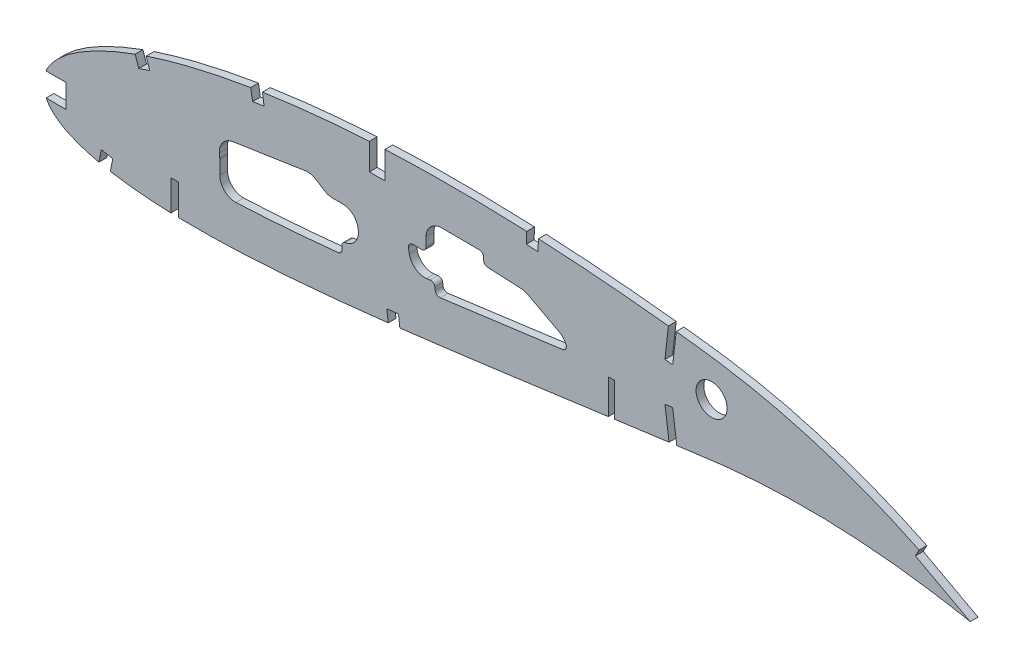
SolidWorks part; units mm, degrees
ref_plane "Front Plane" through (0, 0, 0) normal (0, 0, 1) x (1, 0, 0)
ref_plane "Top Plane" through (0, 0, 0) normal (0, 1, 0) x (1, 0, 0)
ref_plane "Right Plane" through (0, 0, 0) normal (1, 0, 0) x (0, 0, -1)
curve "Curve1"
  spline degree 3 poles (383.949, 0.5986, 0) (383.9196, 0.6168, 0) (383.802, 0.6894, 0) (383.5372, 0.8518, 0) (383.0962, 1.1224, 0) (382.4788, 1.4992, 0) (381.6856, 1.9812, 0) (380.716, 2.5651, 0) (379.5708, 3.249, 0) (378.2502, 4.0295, 0) (376.7543, 4.9032, 0) (375.0838, 5.8664, 0) (373.2387, 6.9137, 0) (371.2197, 8.0407, 0) (369.0276, 9.2423, 0) (366.6628, 10.5128, 0) (364.1261, 11.8459, 0) (361.4185, 13.2358, 0) (358.5405, 14.6749, 0) (355.4934, 16.1571, 0) (352.2782, 17.675, 0) (348.8962, 19.2207, 0) (345.3491, 20.7877, 0) (341.638, 22.3663, 0) (337.765, 23.9497, 0) (333.7318, 25.5289, 0) (329.5407, 27.0966, 0) (325.1933, 28.6428, 0) (320.6929, 30.1607, 0) (316.0417, 31.6403, 0) (311.2431, 33.0737, 0) (306.2997, 34.4516, 0) (301.2157, 35.767, 0) (295.9944, 37.0101, 0) (290.6401, 38.1728, 0) (285.1572, 39.2479, 0) (279.5502, 40.2249, 0) (273.8346, 41.1028, 0) (268.1025, 41.8331, 0) (262.3821, 42.5494, 0) (256.6703, 43.2222, 0) (250.8886, 43.8666, 0) (245.0428, 44.4788, 0) (239.1384, 45.057, 0) (233.1816, 45.5987, 0) (227.1785, 46.1022, 0) (221.135, 46.5647, 0) (215.0573, 46.9856, 0) (208.9515, 47.361, 0) (202.8242, 47.6908, 0) (196.6815, 47.9725, 0) (190.5298, 48.2044, 0) (184.3757, 48.385, 0) (178.2255, 48.5125, 0) (172.0859, 48.5861, 0) (165.9633, 48.6039, 0) (159.8643, 48.5655, 0) (153.7954, 48.4696, 0) (147.7632, 48.3149, 0) (141.7741, 48.1011, 0) (135.8345, 47.8283, 0) (129.951, 47.4942, 0) (124.1299, 47.1009, 0) (118.3778, 46.6469, 0) (112.701, 46.1319, 0) (107.1053, 45.5581, 0) (101.5971, 44.9239, 0) (96.1822, 44.2312, 0) (90.8666, 43.4813, 0) (85.6562, 42.6738, 0) (80.5566, 41.8111, 0) (75.5733, 40.894, 0) (70.7116, 39.9252, 0) (65.9768, 38.9049, 0) (61.3739, 37.8363, 0) (56.9076, 36.7211, 0) (52.5828, 35.5615, 0) (48.4038, 34.3602, 0) (44.375, 33.1199, 0) (40.5009, 31.842, 0) (36.7845, 30.5314, 0) (33.2304, 29.1889, 0) (29.8413, 27.8188, 0) (26.6212, 26.4228, 0) (23.5724, 25.0052, 0) (20.6984, 23.5677, 0) (18.0014, 22.1143, 0) (15.4839, 20.6472, 0) (13.1483, 19.1691, 0) (10.9958, 17.6837, 0) (9.0293, 16.1921, 0) (7.2493, 14.698, 0) (5.6571, 13.2036, 0) (4.255, 11.71, 0) (3.0428, 10.2198, 0) (2.0222, 8.7343, 0) (1.1933, 7.2547, 0) (0.558, 5.7822, 0) (0.1157, 4.3176, 0) (-0.1263, 2.863, 0) (-0.1866, 1.4174, 0) (-0.0621, 0.4718, 0) (0, 0, 0) knots 0 0 0 0 0.000254 0.001015 0.002283 0.004057 0.006331 0.009105 0.012374 0.016134 0.02038 0.025106 0.030306 0.035972 0.0421 0.048678 0.055702 0.06316 0.071046 0.07935 0.088063 0.097176 0.106678 0.116562 0.126814 0.137428 0.148394 0.1597 0.171338 0.183298 0.19557 0.208144 0.221012 0.234162 0.247587 0.261277 0.275223 0.289414 0.303771 0.317689 0.331784 0.34604 0.360444 0.374983 0.38964 0.404403 0.419257 0.434187 0.449177 0.464215 0.479284 0.49437 0.509458 0.524532 0.539579 0.554583 0.56953 0.584403 0.599191 0.613877 0.628447 0.642889 0.657186 0.671326 0.685294 0.699078 0.712665 0.726043 0.739198 0.752118 0.764792 0.777208 0.789356 0.801224 0.812804 0.824083 0.835055 0.84571 0.856038 0.866034 0.875689 0.884998 0.893953 0.902553 0.910789 0.918661 0.926166 0.933303 0.940071 0.946475 0.952518 0.958205 0.963547 0.968557 0.97325 0.977651 0.981787 0.985694 0.989415 0.993001 0.996508 1 1 1 1
curve "Curve2"
  spline degree 3 poles (0, 0, 0) (0.0986, -0.4654, 0) (0.2962, -1.3985, 0) (0.8332, -2.7416, 0) (1.5434, -4.0328, 0) (2.4415, -5.2686, 0) (3.5218, -6.4485, 0) (4.7818, -7.574, 0) (6.2202, -8.6443, 0) (7.8352, -9.659, 0) (9.6244, -10.6191, 0) (11.5859, -11.5241, 0) (13.7178, -12.3737, 0) (16.0178, -13.1667, 0) (18.4831, -13.9043, 0) (21.1113, -14.5848, 0) (23.8995, -15.2091, 0) (26.845, -15.7756, 0) (29.9446, -16.2848, 0) (33.195, -16.7366, 0) (36.593, -17.1311, 0) (40.1351, -17.4676, 0) (43.8179, -17.7467, 0) (47.6377, -17.9687, 0) (51.5909, -18.1343, 0) (55.6735, -18.2428, 0) (59.8817, -18.2959, 0) (64.2115, -18.2945, 0) (68.6589, -18.238, 0) (73.2199, -18.1297, 0) (77.8902, -17.9689, 0) (82.6657, -17.7575, 0) (87.5419, -17.4976, 0) (92.5144, -17.1902, 0) (97.5791, -16.8365, 0) (102.7313, -16.4394, 0) (107.9665, -16, 0) (113.2801, -15.5207, 0) (118.6674, -15.0039, 0) (124.1237, -14.4514, 0) (129.6442, -13.8657, 0) (135.2241, -13.2487, 0) (140.8584, -12.6036, 0) (146.5422, -11.9317, 0) (152.2705, -11.2369, 0) (158.0381, -10.5203, 0) (163.84, -9.7848, 0) (169.6711, -9.0339, 0) (175.5259, -8.2674, 0) (181.3995, -7.4908, 0) (187.2862, -6.7036, 0) (193.1809, -5.9096, 0) (199.0781, -5.1115, 0) (204.9721, -4.3094, 0) (210.8578, -3.5066, 0) (216.7295, -2.7054, 0) (222.5817, -1.9059, 0) (228.409, -1.112, 0) (234.2055, -0.3236, 0) (239.9659, 0.4577, 0) (245.6847, 1.2295, 0) (251.3565, 1.9909, 0) (256.9754, 2.7413, 0) (262.5357, 3.4812, 0) (267.9487, 4.188, 0) (273.2002, 4.8993, 0) (278.3079, 5.4825, 0) (283.3519, 5.9802, 0) (288.3377, 6.3883, 0) (293.259, 6.7125, 0) (298.1104, 6.9553, 0) (302.886, 7.1201, 0) (307.5799, 7.2116, 0) (312.186, 7.2323, 0) (316.6983, 7.1886, 0) (321.1107, 7.0842, 0) (325.4171, 6.9238, 0) (329.6115, 6.7126, 0) (333.688, 6.4566, 0) (337.6405, 6.1594, 0) (341.4634, 5.828, 0) (345.1508, 5.4673, 0) (348.6971, 5.0813, 0) (352.0971, 4.6782, 0) (355.3453, 4.2606, 0) (358.4369, 3.8354, 0) (361.3669, 3.4069, 0) (364.1307, 2.9806, 0) (366.7239, 2.5605, 0) (369.1422, 2.1521, 0) (371.3821, 1.7594, 0) (373.4394, 1.3862, 0) (375.3115, 1.0371, 0) (376.9946, 0.7139, 0) (378.4864, 0.4219, 0) (379.7842, 0.1625, 0) (380.886, -0.0608, 0) (381.79, -0.247, 0) (382.4947, -0.3932, 0) (382.9989, -0.4995, 0) (383.3019, -0.5627, 0) (383.4365, -0.5914, 0) (383.4701, -0.5986, 0) knots 0 0 0 0 0.003638 0.007293 0.011028 0.014901 0.018963 0.023258 0.027821 0.032679 0.037853 0.043362 0.049215 0.055422 0.061989 0.068918 0.076211 0.083868 0.091887 0.100266 0.109 0.118085 0.127515 0.137285 0.147388 0.157816 0.168563 0.179619 0.190977 0.202627 0.21456 0.226767 0.239236 0.251959 0.264924 0.27812 0.291536 0.30516 0.318981 0.332985 0.347163 0.361499 0.375981 0.390597 0.405333 0.420175 0.43511 0.450124 0.465203 0.480333 0.495501 0.51069 0.525887 0.541078 0.556247 0.571382 0.586466 0.601485 0.616424 0.631269 0.646007 0.660621 0.675098 0.689423 0.703582 0.716908 0.730009 0.742952 0.755726 0.76832 0.780724 0.792927 0.804916 0.816679 0.828204 0.839475 0.850481 0.861208 0.871639 0.881763 0.891564 0.901027 0.910139 0.918884 0.927249 0.935221 0.942785 0.949928 0.956638 0.962904 0.968712 0.974054 0.978918 0.983297 0.98718 0.990561 0.993433 0.995791 0.99763 0.998946 0.999737 1 1 1 1
sketch "Sketch1" plane through (0, 0, 0) normal (0, 0, 1) x (1, 0, 0)
  line L23 (383.4597, -0.5986) -> (387.1511, -1.386)
  line L24 (383.9386, 0.5986) -> (387.1511, -1.386)
  spline S4 degree 3 poles (0, 0) (0.0986, -0.4654) (0.2962, -1.3984) (0.8332, -2.7416) (1.5433, -4.0327) (2.4415, -5.2684) (3.5217, -6.4484) (4.7816, -7.5738) (6.22, -8.6441) (7.835, -9.6587) (9.6242, -10.6188) (11.5856, -11.5238) (13.7174, -12.3733) (16.0173, -13.1663) (18.4826, -13.9039) (21.1108, -14.5844) (23.8989, -15.2087) (26.8443, -15.7751) (29.9438, -16.2844) (33.1941, -16.7361) (36.592, -17.1306) (40.134, -17.4671) (43.8167, -17.7462) (47.6365, -17.9682) (51.5895, -18.1338) (55.672, -18.2423) (59.88, -18.2954) (64.2098, -18.294) (68.657, -18.2375) (73.2179, -18.1293) (77.8881, -17.9684) (82.6634, -17.757) (87.5395, -17.4972) (92.5119, -17.1897) (97.5764, -16.836) (102.7286, -16.439) (107.9636, -15.9995) (113.2771, -15.5202) (118.6642, -15.0035) (124.1204, -14.451) (129.6407, -13.8653) (135.2204, -13.2483) (140.8546, -12.6033) (146.5382, -11.9314) (152.2664, -11.2365) (158.0338, -10.52) (163.8356, -9.7845) (169.6665, -9.0336) (175.5212, -8.2672) (181.3946, -7.4906) (187.2811, -6.7034) (193.1757, -5.9095) (199.0727, -5.1113) (204.9666, -4.3092) (210.8521, -3.5065) (216.7237, -2.7054) (222.5757, -1.9059) (228.4028, -1.112) (234.1992, -0.3236) (239.9594, 0.4576) (245.6781, 1.2294) (251.3497, 1.9908) (256.9684, 2.7413) (262.5286, 3.4811) (267.9415, 4.1879) (273.1928, 4.8992) (278.3003, 5.4823) (283.3443, 5.98) (288.3299, 6.3881) (293.2511, 6.7123) (298.1023, 6.9552) (302.8778, 7.1199) (307.5715, 7.2114) (312.1776, 7.2321) (316.6897, 7.1884) (321.102, 7.084) (325.4083, 6.9236) (329.6026, 6.7124) (333.679, 6.4564) (337.6313, 6.1592) (341.4541, 5.8278) (345.1414, 5.4671) (348.6876, 5.0812) (352.0875, 4.6781) (355.3357, 4.2605) (358.4272, 3.8353) (361.3571, 3.4068) (364.1208, 2.9805) (366.7139, 2.5604) (369.1322, 2.1521) (371.372, 1.7594) (373.4293, 1.3862) (375.3013, 1.0371) (376.9844, 0.7139) (378.4761, 0.4219) (379.7739, 0.1625) (380.8757, -0.0608) (381.7796, -0.247) (382.4844, -0.3932) (382.9885, -0.4994) (383.2915, -0.5627) (383.4261, -0.5914) (383.4597, -0.5986) knots 0 0 0 0 0.003638 0.007293 0.011028 0.014901 0.018963 0.023258 0.027821 0.032679 0.037853 0.043362 0.049215 0.055422 0.061989 0.068918 0.076211 0.083868 0.091887 0.100266 0.109 0.118085 0.127515 0.137285 0.147388 0.157816 0.168563 0.179619 0.190977 0.202627 0.21456 0.226767 0.239236 0.251959 0.264924 0.27812 0.291536 0.30516 0.318981 0.332985 0.347163 0.361499 0.375981 0.390597 0.405333 0.420175 0.43511 0.450124 0.465203 0.480333 0.495501 0.51069 0.525887 0.541078 0.556247 0.571382 0.586466 0.601485 0.616424 0.631269 0.646007 0.660621 0.675098 0.689423 0.703582 0.716908 0.730009 0.742952 0.755726 0.76832 0.780724 0.792927 0.804916 0.816679 0.828204 0.839475 0.850481 0.861208 0.871639 0.881763 0.891564 0.901027 0.910139 0.918884 0.927249 0.935221 0.942785 0.949928 0.956638 0.962904 0.968712 0.974054 0.978918 0.983297 0.98718 0.990561 0.993433 0.995791 0.99763 0.998946 0.999737 1 1 1 1
  spline S5 degree 3 poles (383.9386, 0.5986) (383.9092, 0.6167) (383.7916, 0.6893) (383.5268, 0.8518) (383.0858, 1.1223) (382.4685, 1.4991) (381.6752, 1.9811) (380.7057, 2.565) (379.5606, 3.2489) (378.24, 4.0294) (376.7441, 4.9031) (375.0736, 5.8662) (373.2286, 6.9135) (371.2097, 8.0405) (369.0176, 9.242) (366.6529, 10.5125) (364.1162, 11.8456) (361.4087, 13.2354) (358.5307, 14.6745) (355.4837, 16.1566) (352.2687, 17.6745) (348.8867, 19.2201) (345.3398, 20.7871) (341.6288, 22.3657) (337.7559, 23.949) (333.7228, 25.5282) (329.5317, 27.0959) (325.1845, 28.642) (320.6843, 30.1598) (316.0332, 31.6395) (311.2346, 33.0728) (306.2914, 34.4507) (301.2076, 35.766) (295.9864, 37.0091) (290.6322, 38.1717) (285.1495, 39.2469) (279.5426, 40.2238) (273.8272, 41.1017) (268.0952, 41.832) (262.375, 42.5482) (256.6633, 43.2211) (250.8818, 43.8654) (245.0361, 44.4776) (239.1319, 45.0558) (233.1753, 45.5974) (227.1724, 46.1009) (221.129, 46.5635) (215.0515, 46.9843) (208.9459, 47.3597) (202.8187, 47.6895) (196.6762, 47.9712) (190.5246, 48.2031) (184.3707, 48.3836) (178.2206, 48.5111) (172.0812, 48.5848) (165.9588, 48.6026) (159.86, 48.5642) (153.7912, 48.4683) (147.7592, 48.3136) (141.7702, 48.0998) (135.8308, 47.827) (129.9475, 47.4929) (124.1266, 47.0997) (118.3746, 46.6456) (112.6979, 46.1306) (107.1024, 45.5568) (101.5944, 44.9227) (96.1796, 44.23) (90.8641, 43.4801) (85.6539, 42.6727) (80.5544, 41.81) (75.5713, 40.8929) (70.7097, 39.9241) (65.975, 38.9039) (61.3722, 37.8353) (56.906, 36.7201) (52.5814, 35.5606) (48.4025, 34.3593) (44.3738, 33.119) (40.4998, 31.8412) (36.7835, 30.5306) (33.2295, 29.1881) (29.8405, 27.818) (26.6204, 26.4221) (23.5718, 25.0045) (20.6979, 23.5671) (18.0009, 22.1137) (15.4834, 20.6466) (13.148, 19.1685) (10.9955, 17.6833) (9.029, 16.1917) (7.2491, 14.6976) (5.657, 13.2033) (4.2548, 11.7097) (3.0427, 10.2196) (2.0221, 8.734) (1.1932, 7.2545) (0.558, 5.782) (0.1157, 4.3174) (-0.1263, 2.8629) (-0.1866, 1.4173) (-0.0621, 0.4717) (0, 0) knots 0 0 0 0 0.000254 0.001015 0.002283 0.004057 0.006331 0.009105 0.012374 0.016134 0.02038 0.025106 0.030306 0.035972 0.0421 0.048678 0.055702 0.06316 0.071046 0.07935 0.088063 0.097176 0.106678 0.116562 0.126814 0.137428 0.148394 0.1597 0.171338 0.183298 0.19557 0.208144 0.221012 0.234162 0.247587 0.261277 0.275223 0.289414 0.303771 0.317689 0.331784 0.34604 0.360444 0.374983 0.38964 0.404403 0.419257 0.434187 0.449177 0.464215 0.479284 0.49437 0.509458 0.524532 0.539579 0.554583 0.56953 0.584403 0.599191 0.613877 0.628447 0.642889 0.657186 0.671326 0.685294 0.699078 0.712665 0.726043 0.739198 0.752118 0.764792 0.777208 0.789356 0.801224 0.812804 0.824083 0.835055 0.84571 0.856038 0.866034 0.875689 0.884998 0.893953 0.902553 0.910789 0.918661 0.926166 0.933303 0.940071 0.946475 0.952518 0.958205 0.963547 0.968557 0.97325 0.977651 0.981787 0.985694 0.989415 0.993001 0.996508 1 1 1 1
extrude "Boss-Extrude1" add sketch "Sketch1" along normal blind 3.175
sketch "Sketch2" plane through (0, 0, 0) normal (0, 0, -1) x (-1, 0, 0)
  line L0 (-232.8305, 13.2238) -> (-230.2905, 13.2238)
  line L1 (-232.8305, -0.5032) -> (-232.8305, -2.8497)
  line L2 (-232.8305, 13.2238) -> (-232.8305, -0.5032)
  line L4 (-232.8305, -2.8497) -> (-230.2905, -1.6764)
  line L5 (-230.2905, -1.6764) -> (-230.2905, -0.5032)
  line L7 (-139.168, 47.9082) -> (-139.168, 36.8678)
  line L8 (-139.168, 36.8678) -> (-132.818, 36.8678)
  line L9 (-139.168, 47.9082) -> (-139.168, 49.4489)
  line L10 (-55.0305, -5.6829) -> (-55.0305, -17.799)
  line L12 (-139.168, 49.4489) -> (-132.818, 49.1679)
  line L13 (-132.818, 49.1679) -> (-132.818, 47.9082)
  line L14 (-51.8555, -5.6829) -> (-51.8555, -17.799)
  line L16 (-55.0305, -5.6829) -> (-51.8555, -5.6829)
  line L17 (-55.0305, -17.799) -> (-55.0305, -19.968)
  line L19 (-132.818, 47.9082) -> (-132.818, 36.8678)
  line L20 (-55.0305, -19.968) -> (-51.8555, -18.5014)
  line L21 (-51.8555, -18.5014) -> (-51.8555, -17.799)
  line L22 (-230.2905, 13.2238) -> (-230.2905, -0.5032)
extrude "Cut-Extrude1" cut sketch "Sketch2" against normal blind 7.62
sketch "Sketch3" plane through (0, 0, 0) normal (0, 0, -1) x (-1, 0, 0)
  circle A1 centre (-272.4199, 26.2554) radius 6.35
extrude "Cut-Extrude2" cut sketch "Sketch3" against normal blind 7.62
sketch "Sketch4" plane through (0, 0, 3.175) normal (0, 0, 1) x (1, 0, 0)
  line L0 (253.3978, 15.0563) -> (255.0785, 2.468)
  line L1 (253.3978, 15.0563) -> (255.0785, 2.468)
  line L2 (256.5449, 15.4765) -> (253.3978, 15.0563)
  line L3 (256.5449, 15.4765) -> (253.3978, 15.0563)
  line L4 (254.8081, 43.5209) -> (253.3898, 30.9004)
  line L5 (254.8081, 43.5209) -> (253.3898, 30.9004)
  line L6 (197.0245, 48.0319) -> (196.82, 43.2872)
  line L7 (197.0245, 48.0319) -> (196.82, 43.2872)
  line L8 (84.4023, 42.5499) -> (85.1717, 37.8779)
  line L9 (84.4023, 42.5499) -> (85.1717, 37.8779)
  line L10 (139.9591, -7.9331) -> (140.5078, -12.6647)
  line L11 (139.9591, -7.9331) -> (140.5078, -12.6647)
  line L12 (144.6885, -7.3719) -> (139.9591, -7.9331)
  line L13 (144.6885, -7.3719) -> (139.9591, -7.9331)
  line L14 (37.2314, 30.8049) -> (38.732, 26.3414)
  line L15 (37.2314, 30.8049) -> (38.732, 26.3414)
  line L16 (23.4683, -9.9368) -> (22.5446, -14.6116)
  line L17 (23.4683, -9.9368) -> (22.5446, -14.6116)
  line L18 (28.1358, -10.8598) -> (23.4683, -9.9368)
  line L19 (28.1358, -10.8598) -> (23.4683, -9.9368)
  line L20 (-0.4208, 6.5685) -> (9.1042, 6.5685)
  line L21 (-0.4208, 6.5685) -> (9.1042, 6.5685)
  line L22 (9.1042, -2.9565) -> (9.1042, 6.5685)
  line L23 (9.1042, -2.9565) -> (9.1042, 6.5685)
  line L24 (-0.4208, -2.9565) -> (9.1042, -2.9565)
  line L25 (-0.4208, -2.9565) -> (9.1042, -2.9565)
  line L26 (27.1866, -15.6474) -> (28.1358, -10.8598)
  line L27 (27.1866, -15.6474) -> (28.1358, -10.8598)
  line L28 (43.2462, 27.8589) -> (41.731, 32.3666)
  line L29 (43.2462, 27.8589) -> (41.731, 32.3666)
  line L30 (38.732, 26.3414) -> (43.2462, 27.8589)
  line L31 (38.732, 26.3414) -> (43.2462, 27.8589)
  line L32 (89.8796, 38.5972) -> (89.1598, 43.3084)
  line L33 (89.8796, 38.5972) -> (89.1598, 43.3084)
  line L34 (85.1717, 37.8779) -> (89.8796, 38.5972)
  line L35 (85.1717, 37.8779) -> (89.8796, 38.5972)
  line L36 (145.2504, -12.1074) -> (144.6885, -7.3719)
  line L37 (145.2504, -12.1074) -> (144.6885, -7.3719)
  line L38 (201.5767, 43.0552) -> (201.8123, 47.81)
  line L39 (201.5767, 43.0552) -> (201.8123, 47.81)
  line L40 (196.82, 43.2872) -> (201.5767, 43.0552)
  line L41 (196.82, 43.2872) -> (201.5767, 43.0552)
  line L42 (258.2214, 2.8872) -> (256.5449, 15.4765)
  line L43 (258.2214, 2.8872) -> (256.5449, 15.4765)
  line L44 (256.5449, 30.5458) -> (258.0069, 43.1557)
  line L45 (256.5449, 30.5458) -> (258.0069, 43.1557)
  line L46 (253.3898, 30.9004) -> (256.5449, 30.5458)
  line L47 (253.3898, 30.9004) -> (256.5449, 30.5458)
  line L48 (-0.4208, -2.9565) -> (-0.4208, 6.5685)
  line L49 (22.5446, -14.6116) -> (21.6044, -19.3694)
  line L50 (21.6044, -19.3694) -> (26.2707, -20.2914)
  line L51 (26.2707, -20.2914) -> (27.1866, -15.6474)
  line L52 (84.4023, 42.5499) -> (89.1598, 43.3084)
  line L53 (140.5078, -12.6647) -> (145.2504, -12.1074)
  line L54 (197.0245, 48.0319) -> (201.8123, 47.81)
  line L55 (254.8081, 43.5209) -> (258.0069, 43.1557)
  line L56 (255.0785, 2.468) -> (255.3213, 0.6492)
  line L57 (255.3213, 0.6492) -> (258.4684, 1.0693)
  line L58 (258.4684, 1.0693) -> (258.2214, 2.8872)
  spline S0 degree 3 poles (-319.8285, 964.7154) (438.4345, -55.4641) (67.7324, 173.0911) (-130.5432, -104.2984) (209.618, -954.1931) knots -109.467711 -109.467711 -109.467711 -109.467711 0.273428 65.100383 65.100383 65.100383 65.100383 only from (41.731, 32.3666) to (37.2314, 30.8049)
  spline S1 degree 3 poles (41.731, 32.3666) (41.3193, 32.2289) (39.8151, 31.7207) (38.3166, 31.1959) (37.2314, 30.8049) knots 0 0 0 0 0.273428 1 1 1 1
extrude "Cut-Extrude3" cut sketch "Sketch4" against normal through all
sketch "Sketch5" plane through (0, 0, 3.175) normal (0, 0, 1) x (1, 0, 0)
  line L0 (127.2472, 20.1038) -> (116.054, 20.1038)
  line L3 (108.9829, 24.5572) -> (71.3232, 18.8038)
  line L9 (71.7945, 11.0811) -> (71.7945, -1.3909)
  line L10 (121.9103, 2.1782) -> (121.3808, 6.7439)
  line L11 (121.3808, 6.7439) -> (129.4239, 7.6984)
  line L12 (127.2472, 20.1038) -> (129.4239, 7.6984)
  line L13 (125.7357, 28.718) -> (131.3266, -3.1455) construction
  line L14 (79.1937, 35.0998) -> (49.8476, 28.1498) construction
  line L15 (121.3808, 6.7439) -> (149.0188, 10.0236) construction
  line L16 (145.518, 20.1038) -> (116.054, 20.1038) construction
  line L17 (70.732, 22.3937) -> (63.3562, 20.647) construction
  line L18 (71.3232, 18.8038) -> (71.7945, 11.0811)
  line L19 (116.054, 20.1038) -> (108.9829, 24.5572)
  line L20 (126.468, 40.8897) -> (96.4185, 37.8427) construction
  line L21 (116.054, 29.3663) -> (108.3673, 28.5869) construction
  line L22 (150.1388, 10.1565) -> (159.3602, 11.2507)
  line L23 (159.3602, 11.2507) -> (159.9102, 6.616)
  line L24 (213.5265, 13.7782) -> (213.5265, 17.324)
  line L25 (213.5265, 17.324) -> (213.5265, 17.324)
  line L26 (213.5265, 17.324) -> (196.0856, 26.5391)
  line L27 (196.0856, 26.5391) -> (179.3537, 27.3552)
  line L28 (179.3537, 27.3552) -> (179.5415, 31.7126)
  line L29 (155.932, 31.7324) -> (155.932, 20.1038)
  line L30 (131.6947, 7.9678) -> (159.3602, 11.2507) construction
  line L31 (148.3934, 20.1038) -> (150.1388, 10.1565)
  line L32 (146.2503, 32.3176) -> (151.8412, 0.454) construction
  line L33 (155.932, 20.1038) -> (148.3934, 20.1038)
  line L36 (43.0125, 21.0812) -> (53.443, 0.6671) construction
  line L37 (135.993, 30.5178) -> (141.5839, -1.3457) construction
  line L38 (231.5605, 19.5738) -> (198.9045, 36.828) construction
  line L110 (53.443, 0.6671) -> (61.3805, 0.6671) construction
  line L111 (61.3805, 0.6671) -> (61.3805, -11.942) construction
  line L112 (133.4644, -7.0518) -> (132.9219, -2.3736) construction
  line L113 (132.9219, -2.3736) -> (150.2459, -0.3179) construction
  line L114 (150.2459, -0.3179) -> (150.8034, -5.0156) construction
  line L115 (223.9405, 4.6886) -> (223.9405, 19.5738) construction
  line L116 (223.9405, 19.5738) -> (231.5605, 19.5738) construction
  line L125 (198.9045, 36.828) -> (190.204, 37.2524) construction
  line L126 (190.204, 37.2524) -> (190.4019, 41.8451) construction
  line L127 (145.518, 41.8768) -> (145.518, 30.5178) construction
  line L128 (145.518, 30.5178) -> (126.468, 30.5178) construction
  line L129 (126.468, 30.5178) -> (126.468, 40.8897) construction
  line L130 (96.4185, 37.8427) -> (97.1157, 33.279) construction
  line L131 (97.1157, 33.279) -> (79.9261, 30.6529) construction
  line L132 (79.9261, 30.6529) -> (79.1937, 35.0998) construction
  line L133 (49.8476, 28.1498) -> (51.2885, 23.8632) construction
  line L134 (51.2885, 23.8632) -> (43.0125, 21.0812) construction
  line L135 (59.8167, 11.0811) -> (71.7945, 11.0811) construction
  line L136 (57.7836, 15.06) -> (59.8167, 11.0811) construction
  line L137 (64.4778, 17.3103) -> (57.7836, 15.06) construction
  line L138 (63.3562, 20.647) -> (64.4778, 17.3103) construction
  line L139 (71.3232, 18.8038) -> (70.732, 22.3937) construction
  line L140 (116.054, 20.1038) -> (116.054, 29.3663) construction
  line L141 (108.3673, 28.5869) -> (108.9829, 24.5572) construction
  line L142 (155.932, 20.1038) -> (126.468, 20.1038) construction
  spline S0 degree 1 poles (159.9102, 6.616) (213.5265, 13.7782) knots 0 0 1 1 construction
  spline S1 degree 1 poles (179.5415, 31.7126) (155.932, 31.7324) knots 0 0 1 1 construction
  spline S2 degree 1 poles (71.7945, -1.3909) (121.9103, 2.1782) knots 0 0 1 1 construction
  spline S3 degree 3 poles (159.9102, 6.616) (164.3746, 7.1833) (173.2961, 8.3408) (186.698, 10.1292) (200.1064, 11.946) (209.054, 13.1676) (213.5265, 13.7782) knots 0.142323 0.142323 0.142323 0.142323 0.325945 0.509567 0.693189 0.876811 0.876811 0.876811 0.876811
  spline S4 degree 3 poles (179.5415, 31.7126) (177.5729, 31.7494) (173.6348, 31.8061) (167.7311, 31.8388) (161.8287, 31.8179) (157.8978, 31.7672) (155.932, 31.7324) knots 0.237664 0.237664 0.237664 0.237664 0.371263 0.504863 0.638463 0.772063 0.772063 0.772063 0.772063
  spline S5 degree 3 poles (71.7945, -1.3909) (75.9548, -1.2787) (84.2564, -0.9305) (96.788, -0.1167) (109.3347, 0.9275) (117.723, 1.7458) (121.9103, 2.1782) knots 0.147972 0.147972 0.147972 0.147972 0.32451 0.501048 0.677586 0.854123 0.854123 0.854123 0.854123
  spline S36 degree 3 poles (61.3805, -11.942) (67.4058, -11.9519) (73.4269, -11.8005) (85.4632, -11.2817) (91.4772, -10.9139) (103.4919, -10.0249) (109.4942, -9.5033) (121.4867, -8.3518) (127.4774, -7.7211) (133.4644, -7.0518) knots 0 0 0 0 0.25 0.25 0.5 0.5 0.75 0.75 1 1 1 1 construction
  spline S37 degree 3 poles (150.8034, -5.0156) (163.0088, -3.5214) (175.2005, -1.9186) (199.5744, 1.3563) (211.7567, 3.028) (223.9405, 4.6886) knots 0 0 0 0 0.5 0.5 1 1 1 1 construction
  spline S41 degree 3 poles (190.4019, 41.8451) (182.9238, 42.0966) (175.442, 42.2337) (160.4781, 42.2535) (152.996, 42.1371) (145.518, 41.8768) knots 0 0 0 0 0.5 0.5 1 1 1 1 construction
  spline S42 degree 3 poles (126.468, 40.8897) (116.4216, 40.191) (106.3976, 39.1999) (96.4185, 37.8427) knots 0 0 0 0 1 1 1 1 construction
  spline S43 degree 3 poles (79.1937, 35.0998) (74.2467, 34.1892) (69.3194, 33.1701) (59.5289, 30.8714) (54.667, 29.5931) (49.8476, 28.1498) knots 0 0 0 0 0.5 0.5 1 1 1 1 construction
  dimension "D1" = 10.414
  dimension "D2" = 10.414
  dimension "D3" = 10.414
extrude "Cut-Extrude4" cut sketch "Sketch5" against normal blind 7.62
fillet "Fillet1" radius 6.35 11 edges at (150.1388, 10.1565, 1.5875) (213.5265, 17.324, 1.5875) (155.932, 31.7324, 1.5875) (196.0856, 26.5391, 1.5875) (129.4239, 7.6984, 1.5875) (127.2472, 20.1038, 1.5875) (116.054, 20.1038, 1.5875) (108.9829, 24.5572, 1.5875) (71.7945, -1.3909, 1.5875) (71.7945, 11.0811, 1.5875) (71.3232, 18.8038, 1.5875)
fillet "Fillet2" radius 1.778 9 edges at (213.5265, 13.7782, 1.5875) (179.3537, 27.3552, 1.5875) (179.5415, 31.7126, 1.5875) (159.9102, 6.616, 1.5875) (159.3602, 11.2507, 1.5875) (155.932, 20.1038, 1.5875) (148.3934, 20.1038, 1.5875) (121.9103, 2.1782, 1.5875) (121.3808, 6.7439, 1.5875)
sketch "Sketch6" plane through (0, 0, 3.175) normal (0, 0, 1) x (1, 0, 0)
  line L0 (357.0755, 15.3806) -> (355.5684, 12.586)
  line L1 (357.0755, 15.3806) -> (379.4317, 3.3241)
  line L2 (355.5684, 12.586) -> (377.9247, 0.5296)
  line L3 (379.4317, 3.3241) -> (377.9247, 0.5296)
  line L4 (383.4597, -0.5986) -> (387.1511, -1.386) construction
  line L5 (387.1511, -1.386) -> (383.9386, 0.5986) construction
  line L6 (383.4597, -0.5986) -> (387.1511, -1.386)
  line L7 (387.1511, -1.386) -> (383.9386, 0.5986)
  spline S0 degree 3 poles (-542.4415, 1804.8935) (-113.3574, -70.3051) (74.8659, -21.0222) (267.9415, 4.1879) (273.1928, 4.8992) (278.3003, 5.4823) (283.3443, 5.98) (288.3299, 6.3881) (293.2511, 6.7123) (298.1023, 6.9552) (302.8778, 7.1199) (307.5715, 7.2114) (312.1776, 7.2321) (316.6897, 7.1884) (321.102, 7.084) (325.4083, 6.9236) (329.6026, 6.7124) (333.679, 6.4564) (337.6313, 6.1592) (341.4541, 5.8278) (345.1414, 5.4671) (348.6876, 5.0812) (352.0875, 4.6781) (355.3357, 4.2605) (358.4272, 3.8353) (361.3571, 3.4068) (364.1208, 2.9805) (366.7139, 2.5604) (369.1322, 2.1521) (371.372, 1.7594) (373.4293, 1.3862) (375.3013, 1.0371) (376.9844, 0.7139) (378.4761, 0.4219) (379.7739, 0.1625) (380.8757, -0.0608) (381.7796, -0.247) (382.4844, -0.3932) (382.9885, -0.4994) (395.9313, -3.2009) (407.5807, -11.1879) (834.9552, 1947.0393) knots -0.774428 -0.774428 -0.774428 -0.774428 0.689423 0.703582 0.716908 0.730009 0.742952 0.755726 0.76832 0.780724 0.792927 0.804916 0.816679 0.828204 0.839475 0.850481 0.861208 0.871639 0.881763 0.891564 0.901027 0.910139 0.918884 0.927249 0.935221 0.942785 0.949928 0.956638 0.962904 0.968712 0.974054 0.978918 0.983297 0.98718 0.990561 0.993433 0.995791 0.99763 0.998946 0.999737 1.098895 1.098895 1.098895 1.098895 only from (258.2187, 2.9074) to (383.4597, -0.5986) construction
  spline S1 degree 3 poles (1469.2081, 1679.6305) (405.9756, -18.6386) (396.1036, -6.8626) (383.5268, 0.8518) (383.0858, 1.1223) (382.4685, 1.4991) (381.6752, 1.9811) (380.7057, 2.565) (379.5606, 3.2489) (378.24, 4.0294) (376.7441, 4.9031) (375.0736, 5.8662) (373.2286, 6.9135) (371.2097, 8.0405) (369.0176, 9.242) (366.6529, 10.5125) (364.1162, 11.8456) (361.4087, 13.2354) (358.5307, 14.6745) (355.4837, 16.1566) (352.2687, 17.6745) (348.8867, 19.2201) (345.3398, 20.7871) (341.6288, 22.3657) (337.7559, 23.949) (333.7228, 25.5282) (329.5317, 27.0959) (325.1845, 28.642) (320.6843, 30.1598) (316.0332, 31.6395) (311.2346, 33.0728) (306.2914, 34.4507) (301.2076, 35.766) (295.9864, 37.0091) (290.6322, 38.1717) (285.1495, 39.2469) (279.5426, 40.2238) (273.8272, 41.1017) (268.0952, 41.832) (22.2183, 72.6192) (-236.0113, -11.7677) (-104.1696, 1960.0263) knots -0.106155 -0.106155 -0.106155 -0.106155 0.000254 0.001015 0.002283 0.004057 0.006331 0.009105 0.012374 0.016134 0.02038 0.025106 0.030306 0.035972 0.0421 0.048678 0.055702 0.06316 0.071046 0.07935 0.088063 0.097176 0.106678 0.116562 0.126814 0.137428 0.148394 0.1597 0.171338 0.183298 0.19557 0.208144 0.221012 0.234162 0.247587 0.261277 0.275223 0.289414 0.303771 0.317689 2.110646 2.110646 2.110646 2.110646 only from (383.9386, 0.5986) to (257.9959, 43.0613) construction
  spline S2 degree 3 poles (258.2187, 2.9074) (259.6625, 3.0996) (262.9389, 3.5347) (267.9415, 4.1879) (273.1928, 4.8992) (278.3003, 5.4823) (283.3443, 5.98) (288.3299, 6.3881) (293.2511, 6.7123) (298.1023, 6.9552) (302.8778, 7.1199) (307.5715, 7.2114) (312.1776, 7.2321) (316.6897, 7.1884) (321.102, 7.084) (325.4083, 6.9236) (329.6026, 6.7124) (333.679, 6.4564) (337.6313, 6.1592) (341.4541, 5.8278) (345.1414, 5.4671) (348.6876, 5.0812) (352.0875, 4.6781) (355.3357, 4.2605) (358.4272, 3.8353) (361.3571, 3.4068) (364.1208, 2.9805) (366.7139, 2.5604) (369.1322, 2.1521) (371.372, 1.7594) (373.4293, 1.3862) (375.3013, 1.0371) (376.9844, 0.7139) (378.4761, 0.4219) (379.7739, 0.1625) (380.8757, -0.0608) (381.7796, -0.247) (382.4844, -0.3932) (382.9885, -0.4994) (383.2915, -0.5627) (383.4261, -0.5914) (383.4597, -0.5986) knots 0.678267 0.678267 0.678267 0.678267 0.689423 0.703582 0.716908 0.730009 0.742952 0.755726 0.76832 0.780724 0.792927 0.804916 0.816679 0.828204 0.839475 0.850481 0.861208 0.871639 0.881763 0.891564 0.901027 0.910139 0.918884 0.927249 0.935221 0.942785 0.949928 0.956638 0.962904 0.968712 0.974054 0.978918 0.983297 0.98718 0.990561 0.993433 0.995791 0.99763 0.998946 0.999737 1 1 1 1
  spline S3 degree 3 poles (383.9386, 0.5986) (383.9092, 0.6167) (383.7916, 0.6893) (383.5268, 0.8518) (383.0858, 1.1223) (382.4685, 1.4991) (381.6752, 1.9811) (380.7057, 2.565) (379.5606, 3.2489) (378.24, 4.0294) (376.7441, 4.9031) (375.0736, 5.8662) (373.2286, 6.9135) (371.2097, 8.0405) (369.0176, 9.242) (366.6529, 10.5125) (364.1162, 11.8456) (361.4087, 13.2354) (358.5307, 14.6745) (355.4837, 16.1566) (352.2687, 17.6745) (348.8867, 19.2201) (345.3398, 20.7871) (341.6288, 22.3657) (337.7559, 23.949) (333.7228, 25.5282) (329.5317, 27.0959) (325.1845, 28.642) (320.6843, 30.1598) (316.0332, 31.6395) (311.2346, 33.0728) (306.2914, 34.4507) (301.2076, 35.766) (295.9864, 37.0091) (290.6322, 38.1717) (285.1495, 39.2469) (279.5426, 40.2238) (273.8272, 41.1017) (268.0952, 41.832) (262.8117, 42.4936) (259.4638, 42.8908) (257.9959, 43.0613) knots 0 0 0 0 0.000254 0.001015 0.002283 0.004057 0.006331 0.009105 0.012374 0.016134 0.02038 0.025106 0.030306 0.035972 0.0421 0.048678 0.055702 0.06316 0.071046 0.07935 0.088063 0.097176 0.106678 0.116562 0.126814 0.137428 0.148394 0.1597 0.171338 0.183298 0.19557 0.208144 0.221012 0.234162 0.247587 0.261277 0.275223 0.289414 0.303771 0.317689 0.32855 0.32855 0.32855 0.32855
  dimension "D1" = 3.175
  dimension "D2" = 25.4
extrude "Cut-Extrude5" cut sketch "Sketch6" against normal through all contours L3 L1 L0 L2 | L1 S3 | L7 S3 L3 S2 L6 region at (367.5001, 7.9551, 3.175) region at (368.2813, 9.4569, 3.175) region at (381.5092, 0.837, 3.175)
move or copy body "Body-Move/Copy1" [suppressed] bodies to move or copy 120 121 parameters "D1"=0, "D2"=0, "D3"=0
